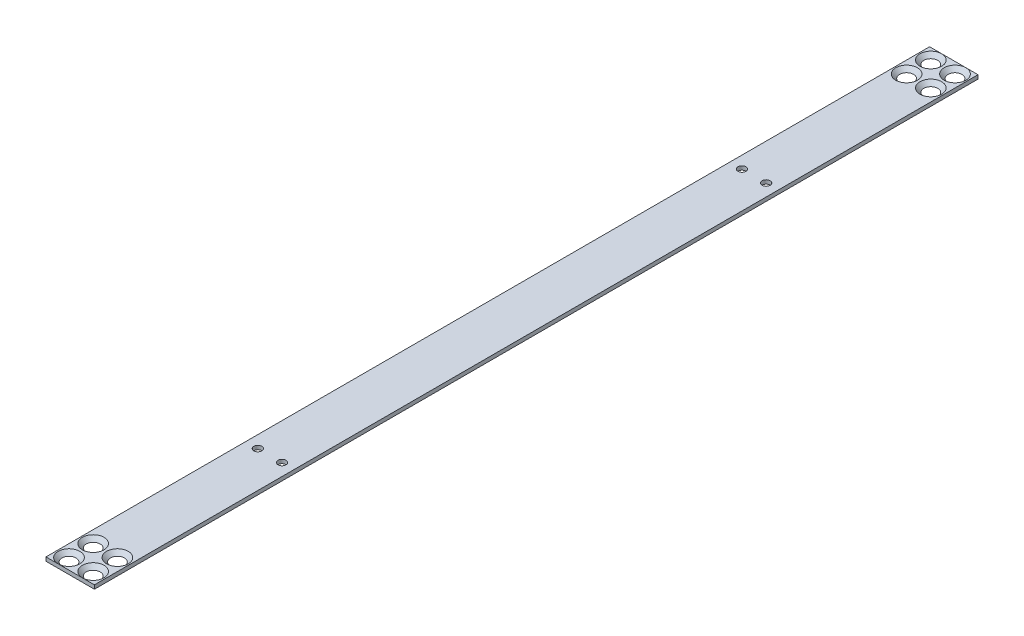
SolidWorks part; units mm, degrees
ref_plane "Front Plane" through (0, 0, 0) normal (0, 0, 1) x (1, 0, 0)
ref_plane "Top Plane" through (0, 0, 0) normal (0, 1, 0) x (1, 0, 0)
ref_plane "Right Plane" through (0, 0, 0) normal (1, 0, 0) x (0, 0, -1)
sketch "Sketch1" plane through (0, 0, 0) normal (0, 1, 0) x (1, 0, 0)
  line L1 (-10, -182.5) -> (10, -182.5)
  line L2 (-10, -182.5) -> (-10, 182.5)
  line L3 (-10, 182.5) -> (10, 182.5)
  line L4 (10, -182.5) -> (10, 182.5)
  line L5 (-10, -182.5) -> (10, 182.5) construction
  line L6 (-10, 182.5) -> (10, -182.5) construction
  point P1 (0, 0)
  dimension "D1" = 365
  dimension "D2" = 20
extrude "Boss-Extrude1" add sketch "Sketch1" along normal blind 1.5875
hole_wizard "CSK for M4 SFHCS1" positions "Sketch2" profile "Sketch3" countersink size "M4" standard "ANSI Metric" end condition through all
sketch "Sketch2" plane through (0, 1.5875, 0) normal (0, 1, 0) x (1, 0, 0)
  line L1 (-5, -178) -> (5, -178)
  line L2 (-5, -178) -> (-5, -168)
  line L3 (-5, -168) -> (5, -168)
  line L4 (5, -178) -> (5, -168)
  line L5 (-5, -178) -> (5, -168) construction
  line L6 (-5, -168) -> (5, -178) construction
  line L7 (-10, -182.5) -> (10, -182.5) construction
  line L8 (-10, 182.5) -> (-10, -182.5) construction
  line L9 (-0.8731, 0) -> (0.8731, 0) construction
  line L10 (-5, 168) -> (5, 178) construction
  line L11 (-5, 178) -> (5, 168) construction
  line L12 (5, 178) -> (5, 168)
  line L13 (-5, 168) -> (5, 168)
  line L14 (-5, 178) -> (-5, 168)
  line L15 (-5, 178) -> (5, 178)
  point P2 (5, -168)
  point P37 (-5, -178)
  point P38 (-5, -168)
  point P39 (5, -178)
  point P45 (0, -173)
  point P54 (5, 178)
  point P55 (-5, 168)
  point P56 (-5, 178)
  point P57 (5, 168)
  dimension "D1" = 10
  dimension "D2" = 4.5
  dimension "D3" = 10
sketch "Sketch3" plane through (5, 1.5875, 168) normal (1, 0, 0) x (0, 0, 1)
  line L0 (0, 0) -> (0, 1.5875)
  line L1 (0, 1.5875) -> (2.25, 1.5875)
  line L2 (2.25, 1.5875) -> (2.25, 2.23)
  line L3 (2.25, 2.23) -> (4.48, 0)
  line L5 (4.48, 0) -> (0, 0)
  line L6 (-2.25, 2.23) -> (-4.48, 0) construction
  line L11 (0, -6.35) -> (0, 107.95) construction
  dimension "Thru Hole Dia." = 4.5
  dimension "Thru Hole Depth" = 1.5875
  dimension "Near C'Sink Dia." = 8.96
  dimension "Near C'Sink Angle" = 90
hole_wizard "M4x0.7 Tapped Hole1" positions "Sketch4" profile "Sketch6" tap size "M4x0.7" standard "ANSI Metric" end condition through all
sketch "Sketch4" plane through (0, 1.5875, 0) normal (0, 1, 0) x (1, 0, 0)
  line L0 (-5, -100) -> (-5, 100)
  line L2 (-10, 182.5) -> (-10, -182.5) construction
  line L3 (0, -0.8731) -> (0, 0.8731) construction
  line L4 (5, -100) -> (5, 100)
  point P1 (-5, -100)
  point P2 (-5, 100)
  point P6 (-5, 0)
  point P18 (5, 100)
  point P19 (5, -100)
  dimension "D1" = 200
  dimension "D2" = 5
sketch "Sketch6" plane through (-5, 1.5875, 100) normal (1, 0, 0) x (0, 0, 1)
  line L0 (0, 0) -> (0, 1.5875)
  line L1 (0, 1.5875) -> (1.65, 1.5875)
  line L2 (1.65, 1.5875) -> (1.65, 0)
  line L5 (1.65, 0) -> (0, 0)
  line L11 (0, -6.35) -> (0, 107.95) construction
  dimension "Thru Tap Drill Dia." = 3.3
  dimension "Thru Tap Drill Depth" = 1.5875
cosmetic thread "Hole Thread1"
cosmetic thread "Hole Thread2"
cosmetic thread "Hole Thread3"
cosmetic thread "Hole Thread4"
